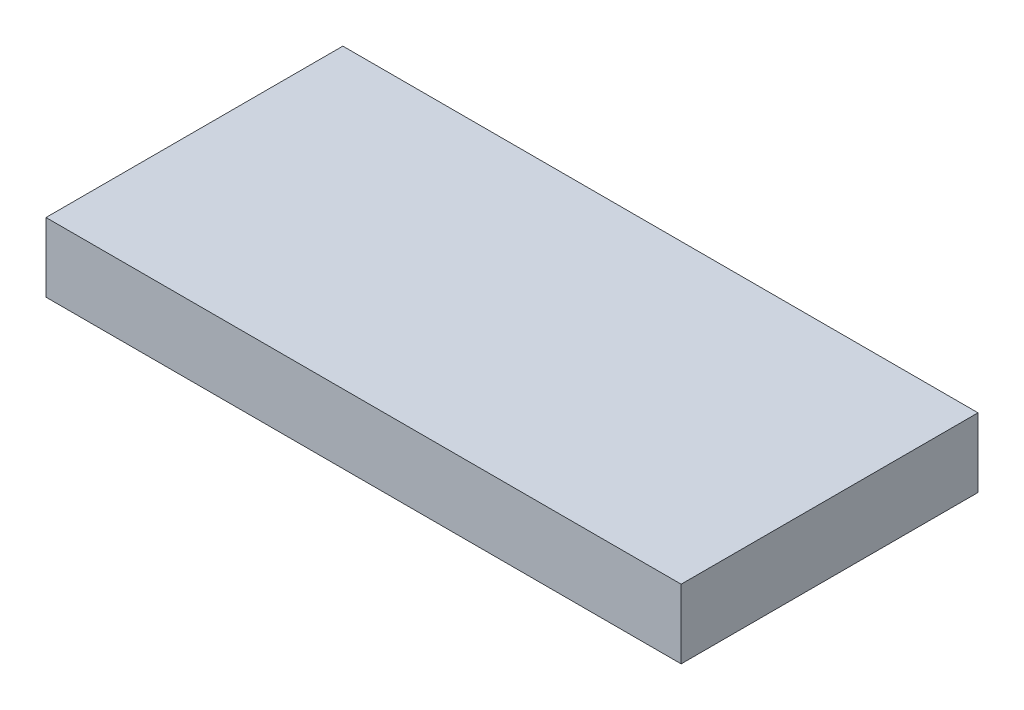
SolidWorks part; units mm, degrees
ref_plane "Front Plane" through (0, 0, 0) normal (0, 0, 1) x (1, 0, 0)
ref_plane "Top Plane" through (0, 0, 0) normal (0, 1, 0) x (1, 0, 0)
ref_plane "Right Plane" through (0, 0, 0) normal (1, 0, 0) x (0, 0, -1)
sketch "Sketch1" plane through (0, 0, 0) normal (0, 1, 0) x (1, 0, 0)
  line L1 (92, 43) -> (-92, 43)
  line L2 (92, 43) -> (92, -43)
  line L3 (92, -43) -> (-92, -43)
  line L4 (-92, 43) -> (-92, -43)
  line L5 (92, 43) -> (-92, -43) construction
  line L6 (92, -43) -> (-92, 43) construction
  point P0 (0, 0)
  dimension "D1" = 184
  dimension "D2" = 86
extrude "base" add sketch "Sketch1" along normal blind 20 contours L1 L4 L3 L2
sketch "Sketch2" plane through (0, 0, 0) normal (0, -1, 0) x (1, 0, 0)
  circle A0 centre (0, 0) radius 5.8
  dimension "D1" = 11.6
extrude "load cell button cut" cut sketch "Sketch2" against normal blind 5.2
equation "\"D2@Sketch1\"=46+40"
equation "\"D1@Sketch1\"=144+40"
